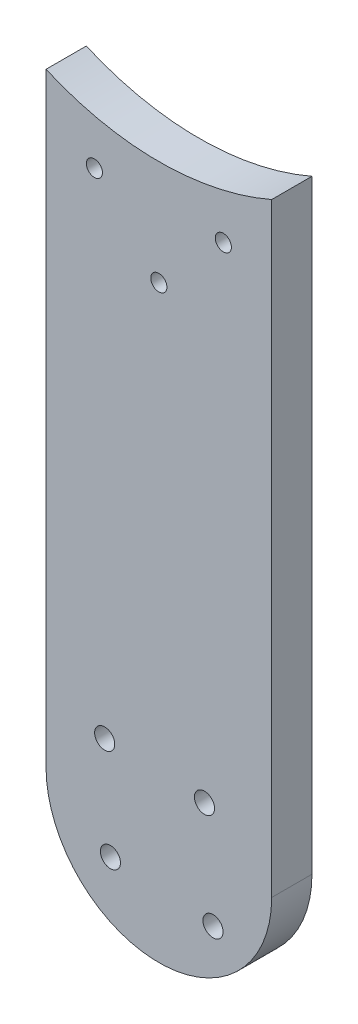
SolidWorks part; units mm, degrees
ref_plane "Front Plane" through (0, 0, 0) normal (0, 0, 1) x (1, 0, 0)
ref_plane "Top Plane" through (0, 0, 0) normal (0, 1, 0) x (1, 0, 0)
ref_plane "Right Plane" through (0, 0, 0) normal (1, 0, 0) x (0, 0, -1)
sketch "Sketch1" plane through (0, 0, 0) normal (0, 0, 1) x (1, 0, 0)
  line L0 (-14, 0) -> (-14, 75)
  line L1 (0, 72.078) -> (0, -14) construction
  line L2 (14, 0) -> (14, 75)
  arc A0 (-14, 0) -> (14, 0) centre (0, 0) ccw
  arc A1 (-14, 75) -> (14, 75) centre (0, 107.078) ccw
  circle A2 centre (-8, 67.376) radius 1
  circle A3 centre (6.72, -6.72) radius 1.25
  circle A4 centre (-6.01, -5.66) radius 1.25
  circle A5 centre (5.66, 6.01) radius 1.25
  circle A6 centre (-6.72, 6.72) radius 1.25
  circle A7 centre (8, 67.376) radius 1
  circle A8 centre (0, 59.0729) radius 1
  dimension "D1" = 2.5
  dimension "D3" = 14
  dimension "D5" = 2
  dimension "D2" = 2
  dimension "D4" = 16
  dimension "D6" = 40.5
  dimension "D7" = 11.53
extrude "Boss-Extrude1" add sketch "Sketch1" along normal blind 5
